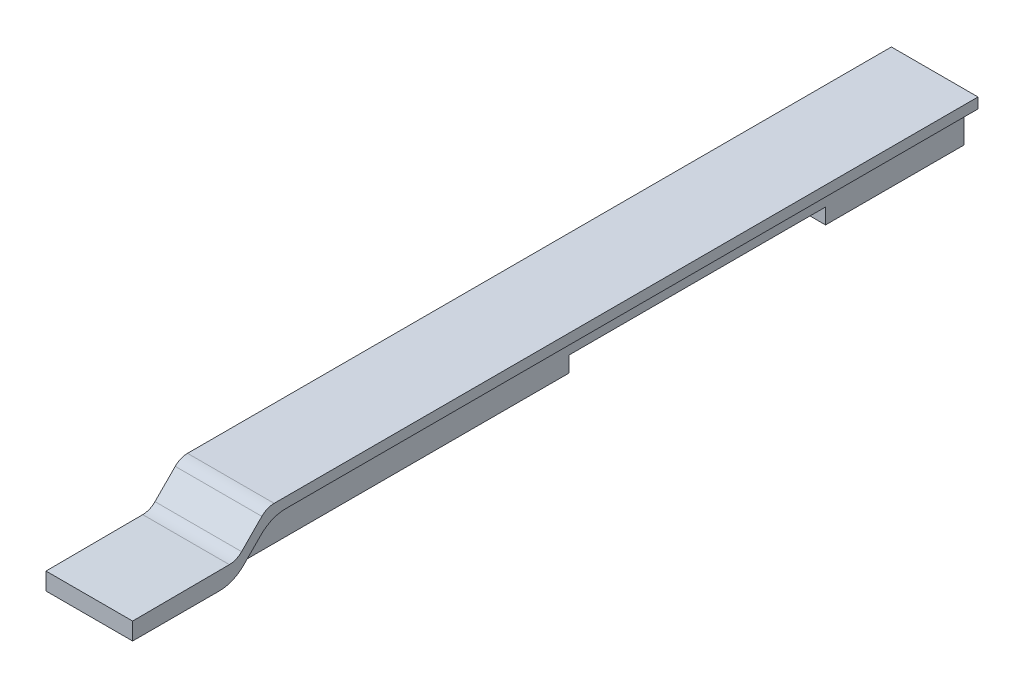
SolidWorks part; units mm, degrees
ref_plane "Front Plane" through (0, 0, 0) normal (0, 0, 1) x (1, 0, 0)
ref_plane "Top Plane" through (0, 0, 0) normal (0, 1, 0) x (1, 0, 0)
ref_plane "Right Plane" through (0, 0, 0) normal (1, 0, 0) x (0, 0, -1)
sketch "Sketch1" plane through (0, 0, 0) normal (1, 0, 0) x (0, 0, -1)
  line L0 (0, 0) -> (-130, 0)
  line L1 (0, 0) -> (74, 0) construction
  line L2 (0, 0) -> (0, 4.5)
  line L3 (0, 4.5) -> (74, 4.5)
  line L4 (74, 4.5) -> (74, 0)
  line L5 (74, 0) -> (114, 0)
  line L6 (-130, 0) -> (-130, 5)
  line L7 (-130, 5) -> (-100.0004, 5.1483)
  line L8 (-100.0004, 5.1483) -> (-91.2357, 14)
  line L11 (114, 14) -> (-91.2357, 14)
  line L12 (114, 0) -> (114, 14)
  point P10 (115.0906, 14.5)
  dimension "D1" = 130
  dimension "D2" = 74
  dimension "D3" = 4.5
  dimension "D4" = 40
  dimension "D5" = 30
  dimension "D6" = 5
  dimension "D7" = 135
  dimension "D8" = 9.5
extrude "Boss-Extrude1" add sketch "Sketch1" along normal blind 25
sketch "Sketch4" plane through (25, 0, 0) normal (1, 0, 0) x (0, 0, -1)
  line L11 (-130, 0) -> (0, 0) construction
  line L12 (-130, 0) -> (0, 0) construction
  line L13 (-100.8762, 0) -> (0, 0)
  line L14 (0, 0) -> (111, 0)
  line L15 (74, 0) -> (114, 0) construction
  line L16 (111, 0) -> (111, 3)
  line L22 (-3, 3) -> (-3, 7.5)
  line L23 (-3, 7.5) -> (77, 7.5)
  line L24 (77, 7.5) -> (77, 3)
  line L25 (77, 3) -> (111, 3)
  line L26 (111, 3) -> (111, 11)
  line L28 (111, 11) -> (-89.9844, 11)
  line L29 (-89.9844, 11) -> (-97.9057, 3)
  line L30 (-97.9057, 3) -> (-3, 3)
  line L35 (111, 3) -> (111, 11)
  line L37 (111, 11) -> (-89.9844, 11)
  line L38 (-89.9844, 11) -> (-100.8762, 0)
  dimension "D1" = 3
ref_plane "Plane1" through (12.5, 0, 0) normal (1, 0, 0) x (0, 0, -1)
sketch "Sketch5" plane through (12.5, 0, 0) normal (1, 0, 0) x (0, 0, -1)
  line L0 (-117.866, 5.06) -> (-112.2372, 10.7447)
  line L1 (-100.0004, 5.1483) -> (-130, 5) construction
  line L2 (-91.2357, 14) -> (-100.0004, 5.1483) construction
  line L3 (-112.2372, 10.7447) -> (-81.8129, 10.7447)
  line L4 (-117.866, 5.06) -> (-95.866, 5.06)
  line L6 (-81.8129, 10.7447) -> (-95.866, 5.06)
  line L11 (-89.9844, 11) -> (-100.8762, 0) construction
  point P6 (0, 0)
  point P9 (0, 0)
  dimension "D1" = 22
  dimension "D2" = 8
sketch "Sketch6" plane through (25, 0, 0) normal (1, 0, 0) x (0, 0, -1)
  line L0 (-130, 0) -> (114, 0) construction
  line L1 (74, 0) -> (114, 0) construction
  line L2 (114, 0) -> (114, 14) construction
  line L3 (-100.8762, 0) -> (114, 0)
  line L4 (114, 0) -> (114, 11)
  line L20 (-3, 3) -> (-3, 7.5)
  line L21 (-3, 7.5) -> (77, 7.5)
  line L22 (77, 7.5) -> (77, 3)
  line L23 (77, 3) -> (111, 3)
  line L24 (111, 3) -> (111, 11)
  line L25 (111, 11) -> (-89.9844, 11)
  line L26 (-89.9844, 11) -> (-97.9057, 3)
  line L27 (-97.9057, 3) -> (-3, 3)
  line L33 (114, 11) -> (-89.9844, 11)
  line L34 (-89.9844, 11) -> (-100.8762, 0)
  point P8 (113.7414, 11)
  point P13 (113.8425, 0)
  dimension "D1" = 3
extrude "Cut-Extrude2" cut sketch "Sketch6" against normal blind 4
mirror "Mirror3" about plane through (12.5, 0, 0) normal (1, 0, 0) of "Cut-Extrude2"
fillet "Fillet6" radius 10 4 edges at (2, 11, 89.9844) (2, 0, 100.8762) (23, 0, 100.8762) (23, 11, 89.9844)
fillet "Fillet7" radius 5 2 edges at (12.5, 14, 91.2357) (12.5, 5.1483, 100.0004)
